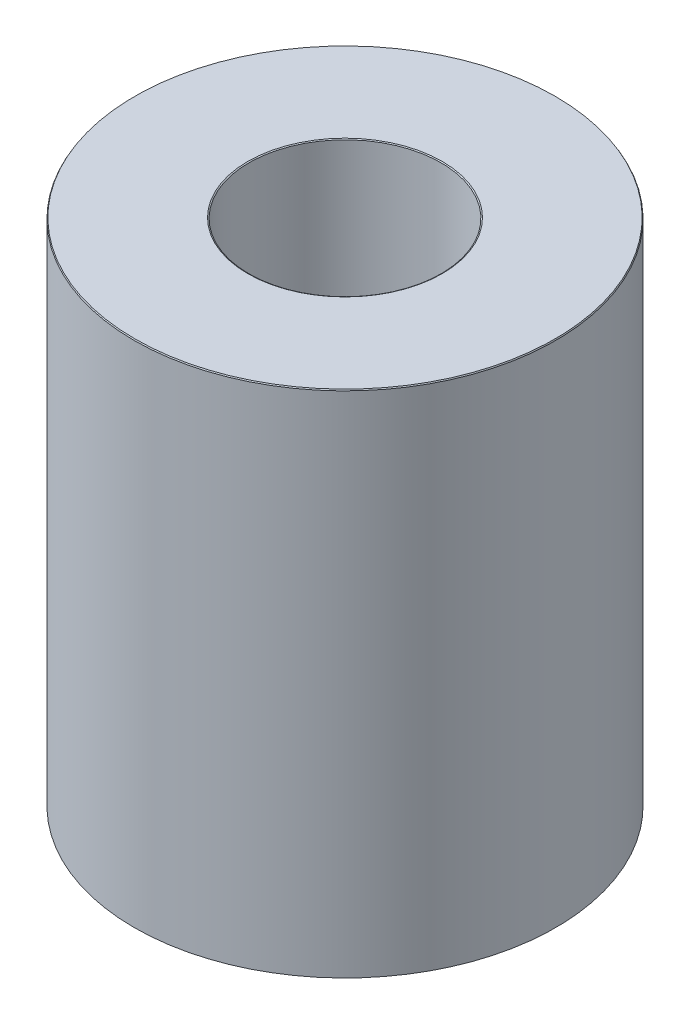
SolidWorks part; units mm, degrees
ref_plane "Front Plane" through (0, 0, 0) normal (0, 0, 1) x (1, 0, 0)
ref_plane "Top Plane" through (0, 0, 0) normal (0, 1, 0) x (1, 0, 0)
ref_plane "Right Plane" through (0, 0, 0) normal (1, 0, 0) x (0, 0, -1)
sketch "Sketch1" plane through (0, 0, 0) normal (0, 1, 0) x (1, 0, 0)
  circle A0 centre (0, 0) radius 45
  dimension "SLEEVE_OD" = 90
extrude "Boss-Extrude1" add sketch "Sketch1" along normal blind 108.9288
sketch "Sketch2" plane through (0, 0, 0) normal (0, 1, 0) x (1, 0, 0)
  circle A0 centre (0, 0) radius 20.5255
  dimension "BORE_D" = 41.0509
extrude "Cut-Extrude1" cut sketch "Sketch2" along normal through all
chamfer "Chamfer1" distance 0.2332 angle 30 4 edges at (0, 108.9288, 20.5255) (0, 0, 20.5255) (0, 0, 45) (0, 108.9288, 45) first distance on face at (0, 108.9288, 20.5255) first distance on face at (0, 0, 20.5255) first distance on face at (0, 108.9288, 45)
